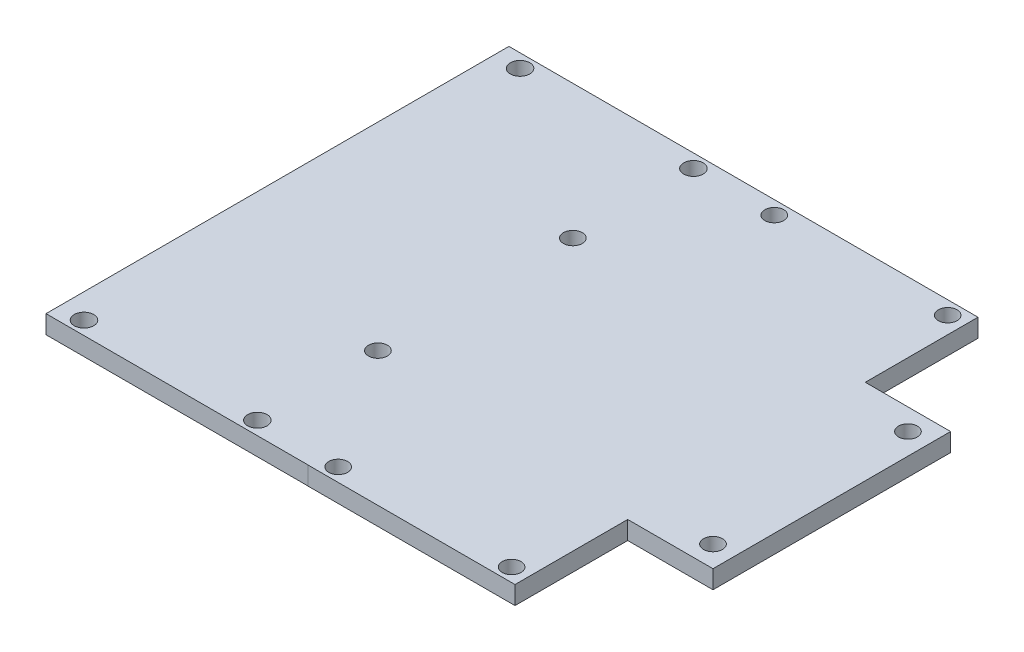
SolidWorks part; units mm, degrees
material "Thornel Mat VMA"
ref_plane "前视基准面" through (0, 0, 0) normal (0, 0, 1) x (1, 0, 0)
ref_plane "上视基准面" through (0, 0, 0) normal (0, 1, 0) x (1, 0, 0)
ref_plane "右视基准面" through (0, 0, 0) normal (1, 0, 0) x (0, 0, -1)
sketch "草图1" plane through (0, 0, 0) normal (0, 1, 0) x (1, 0, 0)
  line L1 (-31, 19.5) -> (31, 19.5)
  line L2 (-31, 19.5) -> (-31, -19.5)
  line L3 (-31, -19.5) -> (31, -19.5)
  line L4 (31, 19.5) -> (31, -19.5)
  line L5 (-31, 19.5) -> (31, -19.5) construction
  line L6 (-31, -19.5) -> (31, 19.5) construction
  line L7 (-27.5, 16) -> (27.5, 16) construction
  line L8 (-27.5, 16) -> (-27.5, -16) construction
  line L9 (-27.5, -16) -> (27.5, -16) construction
  line L10 (27.5, 16) -> (27.5, -16) construction
  line L11 (-27.5, 16) -> (27.5, -16) construction
  line L12 (-27.5, -16) -> (27.5, 16) construction
  line L13 (-14.23, 35.79) -> (14.23, 35.79) construction
  line L14 (-14.23, 35.79) -> (-14.23, -35.79) construction
  line L15 (-14.23, -35.79) -> (14.23, -35.79) construction
  line L16 (14.23, 35.79) -> (14.23, -35.79) construction
  line L17 (-14.23, 35.79) -> (14.23, -35.79) construction
  line L18 (-14.23, -35.79) -> (14.23, 35.79) construction
  line L19 (-17, 38) -> (17, 38)
  line L20 (-17, 38) -> (-17, -38)
  line L21 (-17, -38) -> (17, -38)
  line L22 (17, 38) -> (17, -38)
  line L23 (-17, 38) -> (17, -38) construction
  line L24 (-17, -38) -> (17, 38) construction
  circle A0 centre (-27.5, 16) radius 1.55
  circle A1 centre (27.5, 16) radius 1.55
  circle A2 centre (-27.5, -16) radius 1.55
  circle A3 centre (27.5, -16) radius 1.55
  circle A4 centre (-14.23, 35.79) radius 1.55
  circle A5 centre (14.23, 35.79) radius 1.55
  circle A6 centre (14.23, -35.79) radius 1.55
  circle A7 centre (-14.23, -35.79) radius 1.55
  point P0 (0, 0)
  point P6 (0, 0)
  point P15 (0, 0)
  point P20 (0, 0)
  dimension "D5" = 3.1
  dimension "D6" = 3.1
  dimension "D7" = 3.1
  dimension "D8" = 3.1
  dimension "D11" = 3.1
  dimension "D12" = 3.1
  dimension "D13" = 3.1
  dimension "D14" = 3.1
  dimension "D1" = 39
  dimension "D2" = 62
  dimension "D3" = 32
  dimension "D4" = 55
  dimension "D9" = 28.46
  dimension "D10" = 71.58
  dimension "D15" = 34
  dimension "D16" = 76
extrude "凸台-拉伸1" add sketch "草图1" along normal blind 3 contours L22 L19 L20 L1 A5 A4 | L22 L1 L20 L3 | L20 L1 L2 L3 A2 A0 | L22 L3 L20 L21 A7 A6 | L1 L22 L3 L4 A3 A1 region at (-23.9005, 0, 0) region at (0, 0, -28.5769) region at (0, 0, 0) region at (23.9005, 0, 0) region at (0, 0, 28.5769)
fillet "圆角1" [suppressed] radius 2
sketch "草图3" plane through (0, 3, 0) normal (0, 1, 0) x (1, 0, 0)
  line L0 (-17, 38) -> (-60, 38)
  line L1 (-17, 38) -> (17, 38) construction
  line L2 (-17, 38) -> (-17, 19.5) construction
  line L3 (-60, 38) -> (-60, -37.9854)
  line L4 (-60, -37.9854) -> (-1.4278, -37.9854)
  line L6 (-55.96, 35.79) -> (-27.5, 35.79) construction
  line L7 (-55.96, 35.79) -> (-55.96, -35.79) construction
  line L8 (-55.96, -35.79) -> (-27.5, -35.79) construction
  line L9 (-27.5, 35.79) -> (-27.5, -35.79) construction
  line L10 (-55.96, 35.79) -> (-27.5, -35.79) construction
  line L11 (-55.96, -35.79) -> (-27.5, 35.79) construction
  circle A0 centre (-55.96, 35.79) radius 1.6
  circle A1 centre (-27.5, 35.79) radius 1.6
  circle A2 centre (-55.96, -35.79) radius 1.6
  circle A3 centre (-27.5, -35.79) radius 1.6
  circle A4 centre (-27.5, 16) radius 1.55 construction
  circle A5 centre (-27.5, 16) radius 1.55
  point P8 (-41.73, 0)
  line M6 (-17, 38) -> (-17, 19.5)
  line M7 (-17, 19.5) -> (-31, 19.5)
  line M8 (-31, 19.5) -> (-31, -19.5)
  line M9 (-31, -19.5) -> (-17, -19.5)
  line M10 (-17, -19.5) -> (-17, -38)
  dimension "D6" = 3.2
  dimension "D7" = 3.2
  dimension "D8" = 3.2
  dimension "D9" = 3.2
  dimension "D1" = 71.58
  dimension "D2" = 28.46
  dimension "D3" = 0
  dimension "D4" = 0
  dimension "D5" = 60
extrude "凸台-拉伸2" add sketch "草图3" against normal up to surface (3 mm away) contours L3 L4 L0 A3 A2 A1 A0 M10 M9 M8 M7 M6 region at (-41.4054, 3, -0.0089) up to face at (14.23, 0, -34.24)
